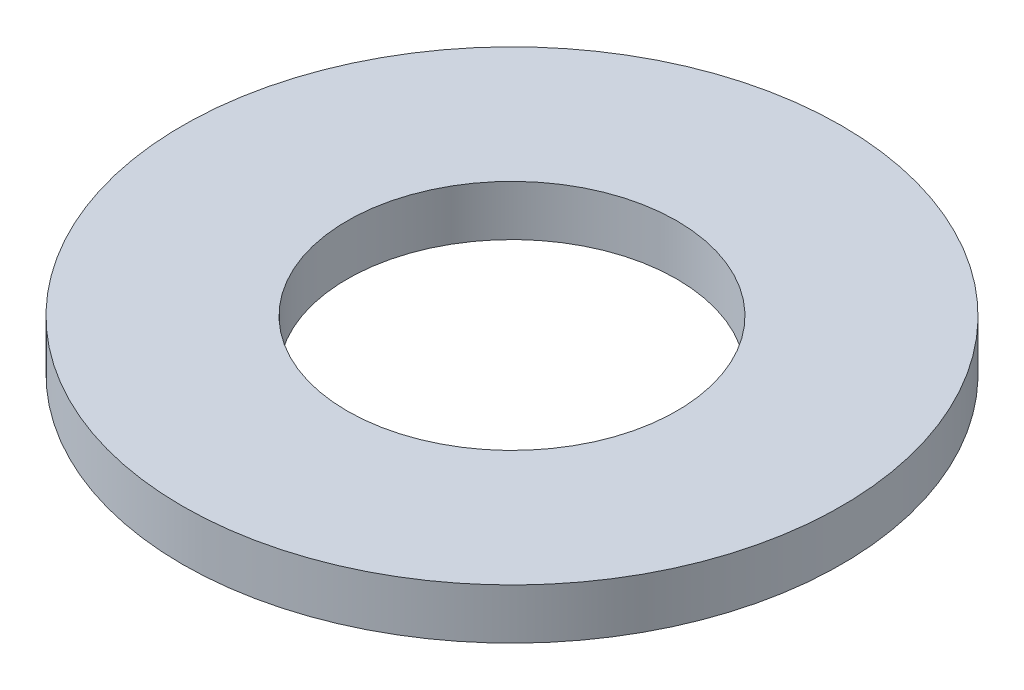
SolidWorks part; units mm, degrees
ref_plane "Front Plane" through (0, 0, 0) normal (0, 0, 1) x (1, 0, 0)
ref_plane "Top Plane" through (0, 0, 0) normal (0, 1, 0) x (1, 0, 0)
ref_plane "Right Plane" through (0, 0, 0) normal (1, 0, 0) x (0, 0, -1)
sketch "Sketch1" plane through (0, 0, 0) normal (0, 1, 0) x (1, 0, 0)
  circle A0 centre (0, 0) radius 85
  dimension "FLANGE_OD" = 170
extrude "Boss-Extrude1" add sketch "Sketch1" along normal blind 13
sketch "Sketch2" plane through (0, 0, 0) normal (0, 1, 0) x (1, 0, 0)
  circle A0 centre (0, 0) radius 42.5
  dimension "BORE_D" = 85
extrude "Cut-Extrude1" cut sketch "Sketch2" along normal through all
sketch "Sketch3" plane through (0, 13, 0) normal (0, 1, 0) x (1, 0, 0)
  circle A0 centre (0, 0) radius 30.6571 construction
  circle A1 centre (-30.6571, 0) radius 6.8311
  dimension "BOLT_D" = 13.6622
  dimension "BOLT_PCD" = 61.3143
extrude "Cut-Extrude2" cut sketch "Sketch3" against normal blind 11.7897 rebuild error yes
pattern_circular "CirPattern1" count 5 over 360 rebuild error yes
